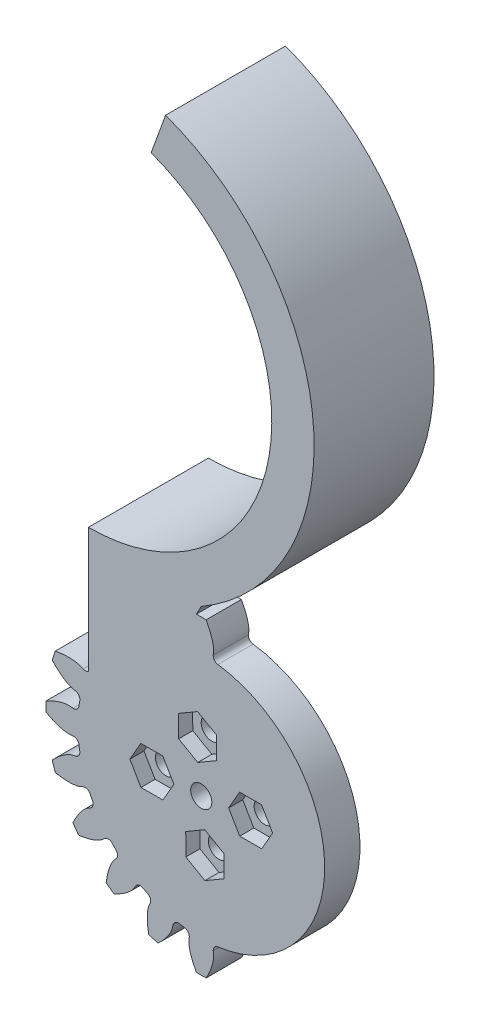
SolidWorks part; units mm, degrees
ref_plane "前视基准面" through (0, 0, 0) normal (0, 0, 1) x (1, 0, 0)
ref_plane "上视基准面" through (0, 0, 0) normal (0, 1, 0) x (1, 0, 0)
ref_plane "右视基准面" through (0, 0, 0) normal (1, 0, 0) x (0, 0, -1)
ref_axis "Axis1" through (0, 0, -88.99) along (0, 0, 1)
sketch "草图1" plane through (0, 0, 0) normal (0, 0, 1) x (1, 0, 0)
  circle A0 centre (0, 0) radius 22
extrude "LaShenA" add sketch "草图1" along normal blind 5
sketch "SketchA" plane through (0, 0, 5) normal (0, 0, 1) x (1, 0, 0)
  line L0 (0, 0) -> (0, 22) construction
  arc A0 (-2.3563, 17.3406) -> (-3.1175, 17.2201) centre (0, 0) ccw
  arc A1 (-0.0193, 23.0469) -> (-7.1036, 21.9249) centre (0, 0) ccw
  arc A2 (-3.1175, 17.2201) -> (-3.9948, 17.8031) centre (-3.2529, 17.9679) cw
  arc A3 (-1.7022, 18.1662) -> (-2.3563, 17.3406) centre (-2.4587, 18.0937) cw
  circle A4 centre (0, 0) radius 18.7939 construction
  circle A5 centre (0, 0) radius 22 construction
  circle A6 centre (0, 0) radius 17.5 construction
  circle A7 centre (0, 0) radius 20 construction
  spline S0 degree 3 poles (-1.7022, 18.1662) (-1.7197, 18.3492) (-1.753, 18.5872) (-1.755, 18.8544) (-1.7481, 18.9686) (-1.7404, 19.0593) (-1.7286, 19.1637) (-1.7121, 19.2816) (-1.69, 19.4129) (-1.6617, 19.5572) (-1.6263, 19.7144) (-1.5833, 19.8841) (-1.5318, 20.0661) (-1.4712, 20.2599) (-1.4008, 20.4653) (-1.3199, 20.6818) (-1.2279, 20.9091) (-1.1241, 21.1465) (-1.0079, 21.3937) (-0.8787, 21.6502) (-0.736, 21.9154) (-0.579, 22.1887) (-0.3453, 22.5712) (-0.1542, 22.8564) (-0.0193, 23.0469) knots 0.125068 0.125068 0.125068 0.125068 0.215847 0.244833 0.257593 0.272674 0.290074 0.309794 0.331834 0.356194 0.382875 0.411875 0.443195 0.476835 0.512796 0.551076 0.591676 0.634597 0.679837 0.727398 0.777278 0.829478 0.883999 1 1 1 1
  spline S1 degree 3 poles (-3.9948, 17.8031) (-4.0347, 17.9825) (-4.0765, 18.2192) (-4.1572, 18.474) (-4.1991, 18.5804) (-4.2344, 18.6643) (-4.2779, 18.76) (-4.33, 18.867) (-4.3916, 18.985) (-4.4632, 19.1135) (-4.5453, 19.252) (-4.6387, 19.4001) (-4.7439, 19.5573) (-4.8615, 19.723) (-4.9919, 19.8965) (-5.1357, 20.0775) (-5.2935, 20.2651) (-5.4655, 20.4589) (-5.6524, 20.6581) (-5.8546, 20.8621) (-6.0723, 21.0702) (-6.306, 21.2817) (-6.6465, 21.5732) (-6.9163, 21.7854) (-7.1036, 21.9249) knots 0.125068 0.125068 0.125068 0.125068 0.215847 0.244833 0.257593 0.272674 0.290074 0.309794 0.331834 0.356194 0.382875 0.411875 0.443195 0.476835 0.512796 0.551076 0.591676 0.634597 0.679837 0.727398 0.777278 0.829478 0.883999 1 1 1 1
  dimension "D1" = 0.76
  dimension "Db" = 37.5877
  dimension "Da" = 44
  dimension "Df" = 35
  dimension "Dn" = 40
extrude "Cut-ExtrudeA" cut sketch "SketchA" against normal blind 50
pattern_circular "www.KYTool.cn" count 20 over 360 about axis through (0, 0, -88.99) along (0, 0, 1) of "Cut-ExtrudeA"
sketch "草图2" plane through (0, 0, 0) normal (0, 0, -1) x (-1, 0, 0)
  line L0 (16, 0) -> (16, 25)
  line L1 (16, 77) -> (16, 83) construction
  line L2 (16, 25) -> (16, 77) construction
  line L3 (16, 51) -> (0, 23.2872) construction
  line L4 (0, 23.2872) -> (0.693, 21.9891)
  line L5 (0.693, 21.9891) -> (0.693, 15.985)
  line L6 (7.1075, 75.432) -> (5.0554, 81.0702)
  line L7 (16, 51) -> (7.1075, 75.432) construction
  arc A0 (16, 0) -> (0.693, 15.985) centre (0, 0) ccw
  arc A1 (7.1075, 75.432) -> (16, 25) centre (16, 51) ccw
  arc A2 (5.0554, 81.0702) -> (0, 23.2872) centre (16, 51) ccw
  arc A3 (16, 19) -> (16, 83) centre (16, 51) ccw construction
  arc A4 (16, 25) -> (16, 77) centre (16, 51) ccw construction
  arc A5 (0.693, 21.9891) -> (-0.693, 21.9891) centre (0, 0) ccw construction
  arc A6 (0.693, 15.985) -> (16, 0) centre (0, 0) ccw construction
  arc A7 (0, 23.2872) -> (16, 19) centre (16, 51) ccw
  arc A8 (16, 77) -> (7.1075, 75.432) centre (16, 51) ccw construction
  arc A9 (16, 83) -> (5.0554, 81.0702) centre (16, 51) ccw construction
  spline S0 degree 3 poles (1.7022, 18.1662) (1.7197, 18.3492) (1.753, 18.5872) (1.755, 18.8544) (1.7481, 18.9686) (1.7404, 19.0593) (1.7286, 19.1637) (1.7121, 19.2816) (1.69, 19.4129) (1.6617, 19.5572) (1.6263, 19.7144) (1.5833, 19.8841) (1.5318, 20.0661) (1.4712, 20.2599) (1.4008, 20.4653) (1.3199, 20.6818) (1.2279, 20.9091) (1.1241, 21.1465) (1.0079, 21.3937) (0.8652, 21.677) (0.7572, 21.8756) (0.693, 21.9891) knots 0.125068 0.125068 0.125068 0.125068 0.215847 0.244833 0.257593 0.272674 0.290074 0.309794 0.331834 0.356194 0.382875 0.411875 0.443195 0.476835 0.512796 0.551076 0.591676 0.634597 0.679837 0.727398 0.792179 0.792179 0.792179 0.792179 construction
  point P5 (16, 51)
  dimension "D1" = 32
  dimension "D4" = 52
  dimension "D2" = 83
  dimension "D3" = 51
  dimension "D5" = 30
  dimension "D6" = 20
extrude "凸台-拉伸3" add sketch "草图2" against normal blind 5 contours L4 L5 A0 L0 A1 L6 A2
sketch "草图3" plane through (0, 0, 0) normal (0, 0, -1) x (-1, 0, 0)
  line L0 (7.1075, 75.432) -> (5.0554, 81.0702) construction
  line L1 (7.1075, 75.432) -> (5.0554, 81.0702)
  line L2 (16, 19) -> (16, 25) construction
  line L4 (16, 25) -> (16, 19)
  arc A0 (7.1075, 75.432) -> (16, 25) centre (16, 51) ccw construction
  arc A1 (5.0554, 81.0702) -> (0, 23.2872) centre (16, 51) ccw construction
  arc A2 (7.1075, 75.432) -> (16, 25) centre (16, 51) ccw
  arc A3 (5.0554, 81.0702) -> (16, 19) centre (16, 51) ccw
  circle A4 centre (16, 51) radius 26 construction
  circle A5 centre (16, 51) radius 32 construction
  circle A6 centre (16, 51) radius 26 construction
extrude "凸台-拉伸4" add sketch "草图3" along normal blind 12
sketch "草图5" plane through (0, 0, 0) normal (0, 0, -1) x (-1, 0, 0)
  line L0 (-2.7376, 17.2845) -> (-5.304, 23.5949)
  line L1 (-5.304, 23.5949) -> (-23.7655, 14.4906)
  line L2 (-23.7655, 14.4906) -> (-24.5242, -9.1132)
  line L3 (-24.5242, -9.1132) -> (-10.1933, -21.9267)
  line L4 (-10.1933, -21.9267) -> (-2.7376, -21.9267)
  line L5 (-2.7376, -21.9267) -> (-2.3563, -17.3406)
  line L6 (16, 13.2346) -> (16, 9.4759)
  line L7 (16, 9.4759) -> (20.5759, 10.1913)
  line L8 (20.5759, 10.1913) -> (20.5759, 14.4906)
  line L9 (20.5759, 14.4906) -> (16, 13.2346)
  circle A0 centre (0, 0) radius 1.5
  circle A1 centre (0.5076, 7) radius 1.5
  circle A2 centre (7, -0.5076) radius 1.5
  circle A3 centre (-0.5076, -7) radius 1.5
  circle A4 centre (-7, 0.5076) radius 1.5
  arc A5 (-2.7376, 17.2845) -> (-2.3563, -17.3406) centre (0, 0) ccw
  arc A6 (-2.3563, 17.3406) -> (-3.1175, 17.2201) centre (0, 0) ccw construction
  point P14 (0, 0)
  dimension "D1" = 3
  dimension "D2" = 3
  dimension "D3" = 7
  dimension "D4" = 4
extrude "切除-拉伸1" cut sketch "草图5" against normal through all
sketch "草图6" plane through (0, 0, 5) normal (0, 0, 1) x (1, 0, 0)
  line L0 (5.4519, -2.1986) -> (8.5696, -2.1861)
  line L1 (2.1986, 5.4519) -> (2.1861, 8.5696)
  line L2 (2.1861, 8.5696) -> (-0.5201, 10.1177)
  line L3 (-0.5201, 10.1177) -> (-3.2138, 8.5481)
  line L4 (-3.2138, 8.5481) -> (-3.2014, 5.4304)
  line L5 (-3.2014, 5.4304) -> (-0.4952, 3.8823)
  line L6 (-0.4952, 3.8823) -> (2.1986, 5.4519)
  line L7 (8.5696, -2.1861) -> (10.1177, 0.5201)
  line L8 (10.1177, 0.5201) -> (8.5481, 3.2138)
  line L9 (8.5481, 3.2138) -> (5.4304, 3.2014)
  line L10 (5.4304, 3.2014) -> (3.8823, 0.4952)
  line L11 (3.8823, 0.4952) -> (5.4519, -2.1986)
  line L12 (-2.1986, -5.4519) -> (-2.1861, -8.5696)
  line L13 (-2.1861, -8.5696) -> (0.5201, -10.1177)
  line L14 (0.5201, -10.1177) -> (3.2138, -8.5481)
  line L15 (3.2138, -8.5481) -> (3.2014, -5.4304)
  line L16 (3.2014, -5.4304) -> (0.4952, -3.8823)
  line L17 (0.4952, -3.8823) -> (-2.1986, -5.4519)
  line L18 (-5.4519, 2.1986) -> (-8.5696, 2.1861)
  line L19 (-8.5696, 2.1861) -> (-10.1177, -0.5201)
  line L20 (-10.1177, -0.5201) -> (-8.5481, -3.2138)
  line L21 (-8.5481, -3.2138) -> (-5.4304, -3.2014)
  line L22 (-5.4304, -3.2014) -> (-3.8823, -0.4952)
  line L23 (-3.8823, -0.4952) -> (-5.4519, 2.1986)
  circle A0 centre (-0.5076, 7) radius 2.7 construction
  point P30 (0, 0)
  dimension "D1" = 5.4
  dimension "D2" = 4
extrude "切除-拉伸2" cut sketch "草图6" against normal blind 2
